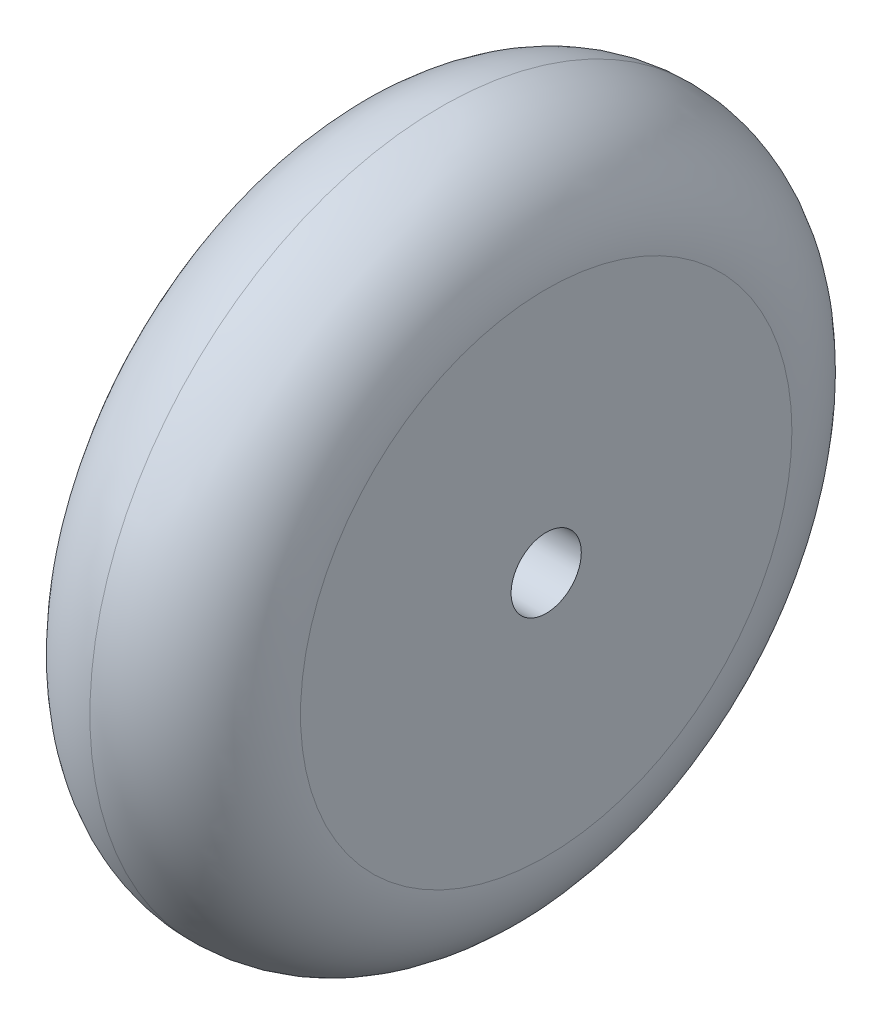
SolidWorks part; units mm, degrees
ref_plane "Front Plane" through (0, 0, 0) normal (0, 0, 1) x (1, 0, 0)
ref_plane "Top Plane" through (0, 0, 0) normal (0, 1, 0) x (1, 0, 0)
ref_plane "Right Plane" through (0, 0, 0) normal (1, 0, 0) x (0, 0, -1)
sketch "Sketch1" plane through (0, 0, 0) normal (1, 0, 0) x (0, 0, -1)
  circle A0 centre (0, 0) radius 40
  circle A1 centre (0, 0) radius 4
  dimension "D1" = 80
  dimension "D2" = 8
extrude "Boss-Extrude1" add sketch "Sketch1" along normal blind 24
fillet "Fillet1" radius 12 2 edges at (24, 0, -40) (0, 0, -40)
